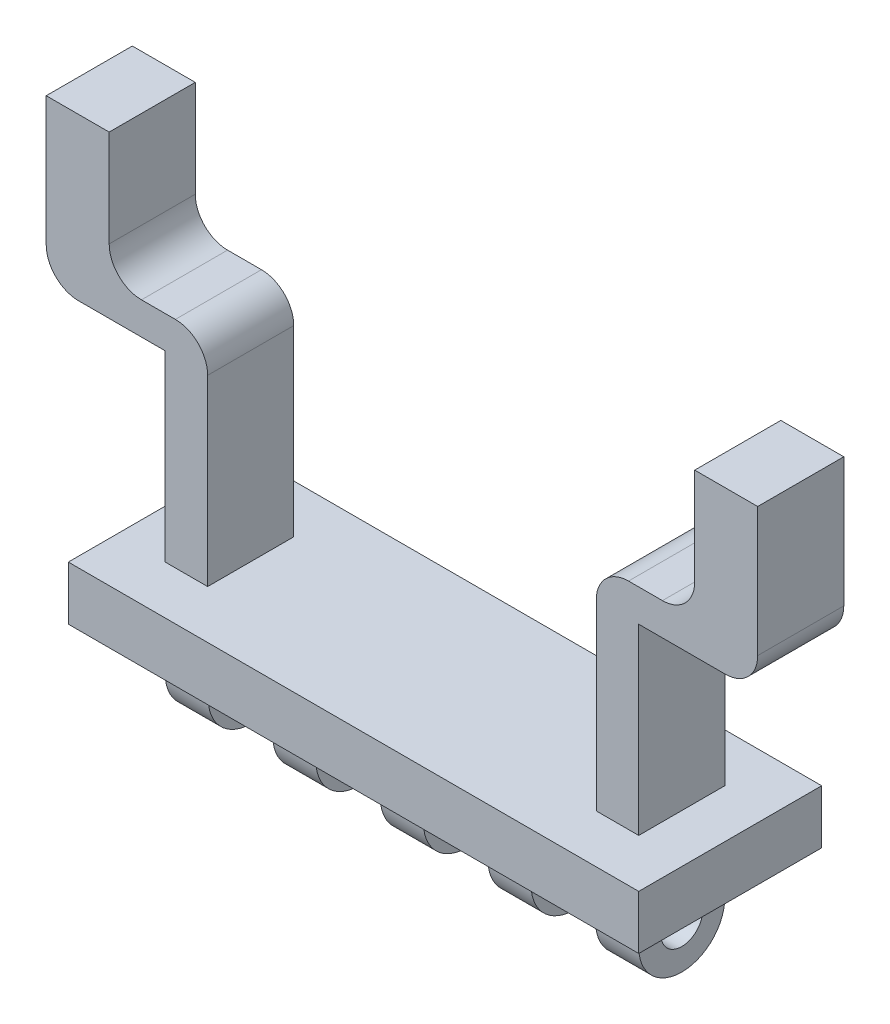
SolidWorks part; units mm, degrees
ref_plane "Front Plane" through (0, 0, 0) normal (0, 0, 1) x (1, 0, 0)
ref_plane "Top Plane" through (0, 0, 0) normal (0, 1, 0) x (1, 0, 0)
ref_plane "Right Plane" through (0, 0, 0) normal (1, 0, 0) x (0, 0, -1)
sketch "Sketch1" plane through (0, 0, 0) normal (0, 1, 0) x (1, 0, 0)
  line L1 (-22, 4) -> (22, 4)
  line L2 (-22, 4) -> (-22, -4)
  line L3 (-22, -4) -> (22, -4)
  line L4 (22, 4) -> (22, -4)
  line L5 (-22, 4) -> (22, -4) construction
  line L6 (-22, -4) -> (22, 4) construction
  point P0 (0, 0)
extrude "Boss-Extrude1" add sketch "Sketch1" along normal blind 5
sketch "Sketch2" plane through (0, 5, 0) normal (0, 1, 0) x (1, 0, 0)
  line L0 (-22, -4) -> (22, -4) construction
  line L1 (22, 4) -> (18.0543, 4)
  line L2 (22, 4) -> (22, -4)
  line L3 (22, -4) -> (18.0543, -4)
  line L4 (18.0543, 4) -> (18.0543, -4)
  line L5 (20.0272, -4) -> (20.0272, 4) construction
  line L6 (22, 0) -> (18.0543, 0) construction
  point P224 (20.0272, 0)
extrude "Boss-Extrude2" add sketch "Sketch2" along normal blind 17
ref_plane "Plane1" through (18.0543, 0, 0) normal (-1, 0, 0) x (0, 0, 1)
sketch "Sketch3" plane through (18.0543, 0, 0) normal (-1, 0, 0) x (0, 0, 1)
  line L1 (4, 22) -> (-4, 22)
  line L2 (4, 22) -> (4, 25)
  line L3 (4, 25) -> (-4, 25)
  line L4 (-4, 22) -> (-4, 25)
  line L5 (0, 25) -> (0, 22) construction
  line L6 (4, 23.5) -> (-4, 23.5) construction
  point P656 (0, 23.5)
  dimension "D1" = 3
extrude "Boss-Extrude3" add sketch "Sketch3" against normal blind 15
sketch "Sketch4" plane through (0, 25, 0) normal (0, 1, 0) x (1, 0, 0)
  line L0 (33.0543, -4) -> (18.0543, -4) construction
  line L1 (27.2037, -4) -> (33.0543, -4)
  line L2 (27.2037, -4) -> (27.2037, 4)
  line L3 (27.2037, 4) -> (33.0543, 4)
  line L4 (33.0543, -4) -> (33.0543, 4)
  line L5 (30.129, 4) -> (30.129, -4) construction
  line L6 (27.2037, 0) -> (33.0543, 0) construction
  point P416 (30.129, 0)
extrude "Boss-Extrude4" add sketch "Sketch4" along normal blind 12
mirror "Mirror1" about plane through (0, 0, 0) normal (1, 0, 0) of "Boss-Extrude4", "Boss-Extrude3", "Boss-Extrude2"
sketch "Sketch5" plane through (0, 0, 0) normal (0, -1, 0) x (1, 0, 0)
  line L0 (22, -4) -> (-22, -4) construction
  line L1 (22, 4) -> (18, 4)
  line L2 (22, 4) -> (22, -4)
  line L3 (22, -4) -> (18, -4)
  line L4 (18, 4) -> (18, -4)
  line L5 (20, -4) -> (20, 4) construction
  line L6 (22, 0) -> (18, 0) construction
  point P816 (20, 0)
  dimension "D1" = 4
extrude "Boss-Extrude5" add sketch "Sketch5" along normal blind 8
fillet "Fillet2" radius 4 2 edges at (20, -8, -4) (20, -8, 4)
pattern_linear "LPattern1" count 5 spacing 10 along (-1, 0, 0) of "Boss-Extrude5", "Fillet2"
sketch "Sketch6" plane through (22, 0, 0) normal (1, 0, 0) x (0, 0, -1)
  circle A0 centre (0, -4) radius 1.9413
  arc A1 (-4, -4) -> (0, -8) centre (0, -4) ccw construction
  dimension "D1" = 0
extrude "Cut-Extrude1" cut sketch "Sketch6" against normal through all
sketch "Sketch7" plane through (0, 0, 4) normal (0, 0, 1) x (1, 0, 0)
  line L0 (22, 22) -> (22, -4) construction
  line L1 (22, 5) -> (-22, 5)
  line L2 (22, 5) -> (22, 0)
  line L3 (22, 0) -> (-22, 0)
  line L4 (-22, 5) -> (-22, 0)
  line L5 (0, 0) -> (0, 5) construction
  line L6 (22, 2.5) -> (-22, 2.5) construction
  line L7 (-22, 22) -> (-22, -4) construction
  point P768 (0, 2.5)
extrude "Boss-Extrude6" add sketch "Sketch7" along normal blind 4.5
sketch "Sketch8" plane through (-22, 0, 0) normal (-1, 0, 0) x (0, 0, 1)
  line L0 (-4, 22) -> (-4, -4) construction
  line L1 (8.5, 5) -> (-4, 5)
  line L2 (8.5, 5) -> (8.5, 0)
  line L3 (8.5, 0) -> (-4, 0)
  line L4 (-4, 5) -> (-4, 0)
  line L5 (2.25, 0) -> (2.25, 5) construction
  line L6 (8.5, 2.5) -> (-4, 2.5) construction
  point P240 (2.25, 2.5)
extrude "Boss-Extrude7" add sketch "Sketch8" along normal blind 4.5
sketch "Sketch9" plane through (0, 0, -4) normal (0, 0, -1) x (-1, 0, 0)
  line L0 (-22, 22) -> (-22, -4) construction
  line L1 (26.5, 5) -> (-22, 5)
  line L2 (26.5, 5) -> (26.5, 0)
  line L3 (26.5, 0) -> (-22, 0)
  line L4 (-22, 5) -> (-22, 0)
  line L5 (2.25, 0) -> (2.25, 5) construction
  line L6 (26.5, 2.5) -> (-22, 2.5) construction
  point P660 (2.25, 2.5)
extrude "Boss-Extrude8" add sketch "Sketch9" along normal blind 4.5
sketch "Sketch10" plane through (22, 0, 0) normal (1, 0, 0) x (0, 0, -1)
  line L1 (-8.5, 5) -> (8.5, 5)
  line L2 (-8.5, 5) -> (-8.5, 0)
  line L3 (-8.5, 0) -> (8.5, 0)
  line L4 (8.5, 5) -> (8.5, 0)
  line L5 (0, 0) -> (0, 5) construction
  line L6 (-8.5, 2.5) -> (8.5, 2.5) construction
  point P356 (0, 2.5)
extrude "Boss-Extrude9" add sketch "Sketch10" along normal blind 4.5
fillet "Fillet4" radius 3 6 edges at (-27.2037, 25, 0) (-33.0543, 22, 0) (-18.0543, 25, 0) (27.2037, 25, 0) (18.0543, 25, 0) (33.0543, 22, 0)
